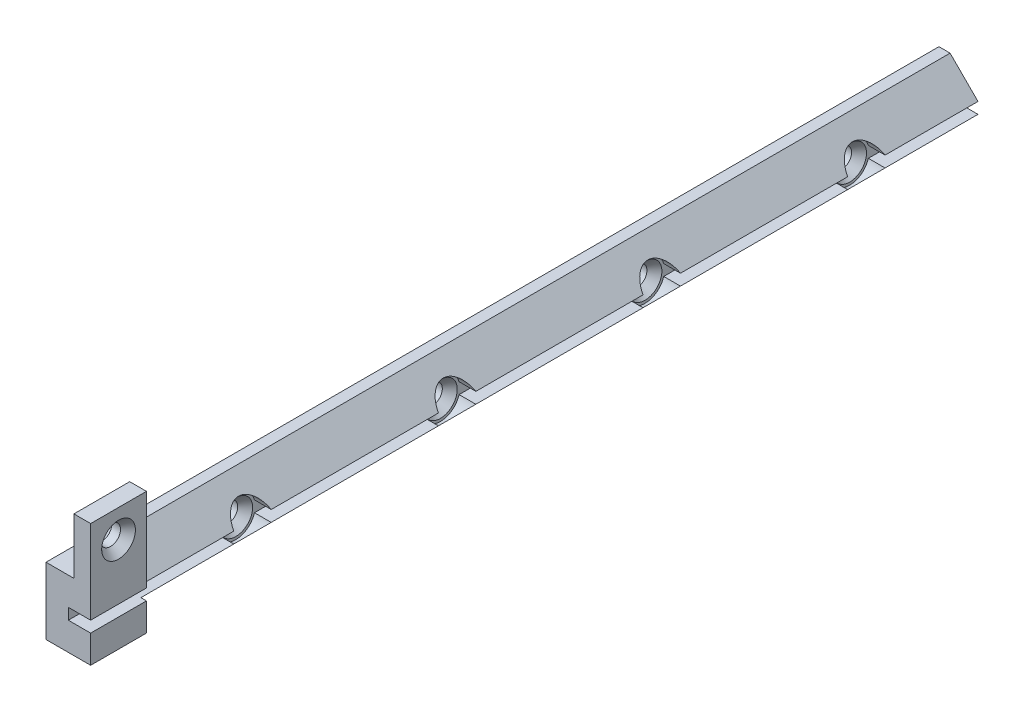
SolidWorks part; units mm, degrees
ref_plane "Front Plane" through (0, 0, 0) normal (0, 0, 1) x (1, 0, 0)
ref_plane "Top Plane" through (0, 0, 0) normal (0, 1, 0) x (1, 0, 0)
ref_plane "Right Plane" through (0, 0, 0) normal (1, 0, 0) x (0, 0, -1)
sketch "Sketch1" plane through (0, 0, 0) normal (0, 0, 1) x (1, 0, 0)
  line L0 (-2, 0) -> (0, 0) construction
  line L1 (-2, -3) -> (2, -3)
  line L2 (-2, -3) -> (-2, 3)
  line L3 (-2, 3) -> (2, 3)
  line L4 (2, -3) -> (2, -0.5)
  line L5 (-2, -3) -> (2, 3) construction
  line L6 (-2, 3) -> (2, -3) construction
  line L7 (2, 0.5) -> (0, 0.5)
  line L9 (2, -0.5) -> (0, -0.5)
  line L10 (0, 0.5) -> (0, -0.5)
  line L11 (2, 0.5) -> (2, 3)
  point P0 (0, 0)
  dimension "D1" = 1
  dimension "D2" = 6
  dimension "D3" = 2
  dimension "D4" = 4
extrude "Boss-Extrude1" add sketch "Sketch1" along normal blind 75
sketch "Sketch5" plane through (2, 0, 0) normal (1, 0, 0) x (0, 0, -1)
  line L1 (-75, 0) -> (0, 0) construction
  line L4 (-75, -0.5) -> (-75, 0.5) construction
  circle A0 centre (-65, 0) radius 1.75
  circle A1 centre (-46.6667, 0) radius 1.75
  circle A2 centre (-28.3333, 0) radius 1.75
  circle A3 centre (-10, 0) radius 1.75
  point P6 (-65, 0)
  dimension "D1" = 3.5
  dimension "D2" = 10
  dimension "D3" = 10
  dimension "D5" = 4
extrude "Cut-Extrude1" cut sketch "Sketch5" against normal up to surface (2 mm away) up to face at (0, 0, 37.5)
hole_wizard "CSK for #0 Flat Head Machine Screw2" positions "Sketch4" profile "Sketch2" countersink size "#0" standard "ANSI Inch"
sketch "Sketch4" plane through (0, 0, 0) normal (1, 0, 0) x (0, 0, -1)
  arc A0 (-63.3229, 0.5) -> (-66.6771, 0.5) centre (-65, 0) ccw construction
  arc A3 (-44.9896, 0.5) -> (-48.3437, 0.5) centre (-46.6667, 0) ccw construction
  arc A4 (-8.323, 0.5) -> (-11.6771, 0.5) centre (-10, 0) ccw construction
  point P0 (-65, 0)
  point P2 (-10, 0)
  point P4 (-46.6667, 0)
  point P25 (-28.3333, 0)
sketch "Sketch2" plane through (0, 0, 65) normal (0, 1, 0) x (0, 0, -1)
  line L0 (0, 0) -> (0, 3.8362)
  line L1 (0, 3.8362) -> (0.889, 3.302)
  line L2 (0.889, 3.302) -> (0.889, 0.7159)
  line L3 (0.889, 0.7159) -> (1.5113, 0)
  line L5 (1.5113, 0) -> (0, 0)
  line L6 (-0.889, 0.7159) -> (-1.5113, 0) construction
  line L10 (0, 3.8362) -> (-0.889, 3.302) construction
  line L11 (0, -6.35) -> (0, 107.95) construction
  dimension "Hole Dia." = 1.778
  dimension "Hole Depth" = 3.302
  dimension "Near C'Sink Dia." = 3.0226
  dimension "Near C'Sink Angle" = 82
  dimension "Drill Angle" = 118
chamfer "Chamfer1" distance 3 angle 45 2 edges at (2, -3, 37.5) (2, 3, 37.5)
sketch "Sketch6" plane through (0, 0, 75) normal (0, 0, 1) x (1, 0, 0)
  line L0 (-2, -3) -> (-1, -3) construction
  line L1 (2, 3) -> (2, 0.5)
  line L2 (-2, 3) -> (-2, -3)
  line L3 (-2, -3) -> (2, -3)
  line L5 (-2, 3) -> (-2, -3) construction
  line L6 (2, -0.5) -> (2, -3)
  line L7 (2, 0.5) -> (0, 0.5)
  line L8 (0, 0.5) -> (1.5, 0.5) construction
  line L9 (2, -0.5) -> (0, -0.5)
  line L10 (0, 0.5) -> (0, -0.5)
  line L11 (-2, 3) -> (2, 3)
  line L12 (-1, 3) -> (-2, 3) construction
  line L13 (2, 3) -> (0.5, 3)
  line L14 (2, 3) -> (2, 8)
  line L15 (2, 8) -> (0.5, 8)
  line L16 (0.5, 3) -> (0.5, 8)
  dimension "D1" = 2.5
  dimension "D2" = 4
  dimension "D3" = 5
  dimension "D4" = 1.5
extrude "Boss-Extrude2" add sketch "Sketch6" along normal blind 5
hole_wizard "CSK for #0 Flat Head Machine Screw1" positions "Sketch8" profile "Sketch7" countersink size "#0" standard "ANSI Inch"
sketch "Sketch8" plane through (2, 0, 0) normal (1, 0, 0) x (0, 0, -1)
  line L1 (-80, 3) -> (-75, 3) construction
  line L2 (-80, 3) -> (-80, 8) construction
  line L3 (-80, 8) -> (-75, 8) construction
  line L4 (-75, 3) -> (-75, 8) construction
  line L5 (-80, 3) -> (-75, 8) construction
  line L6 (-80, 8) -> (-75, 3) construction
  point P0 (-77.5, 5.5)
  point P4 (-77.5, 5.5)
  dimension "D1" = 5
sketch "Sketch7" plane through (2, 5.5, 77.5) normal (0, 1, 0) x (0, 0, -1)
  line L0 (0, 0) -> (0, 3.8362)
  line L1 (0, 3.8362) -> (0.889, 3.302)
  line L2 (0.889, 3.302) -> (0.889, 0.7159)
  line L3 (0.889, 0.7159) -> (1.5113, 0)
  line L5 (1.5113, 0) -> (0, 0)
  line L6 (-0.889, 0.7159) -> (-1.5113, 0) construction
  line L10 (0, 3.8362) -> (-0.889, 3.302) construction
  line L11 (0, -6.35) -> (0, 107.95) construction
  dimension "Hole Dia." = 1.778
  dimension "Hole Depth" = 3.302
  dimension "Near C'Sink Dia." = 3.0226
  dimension "Near C'Sink Angle" = 82
  dimension "Drill Angle" = 118
